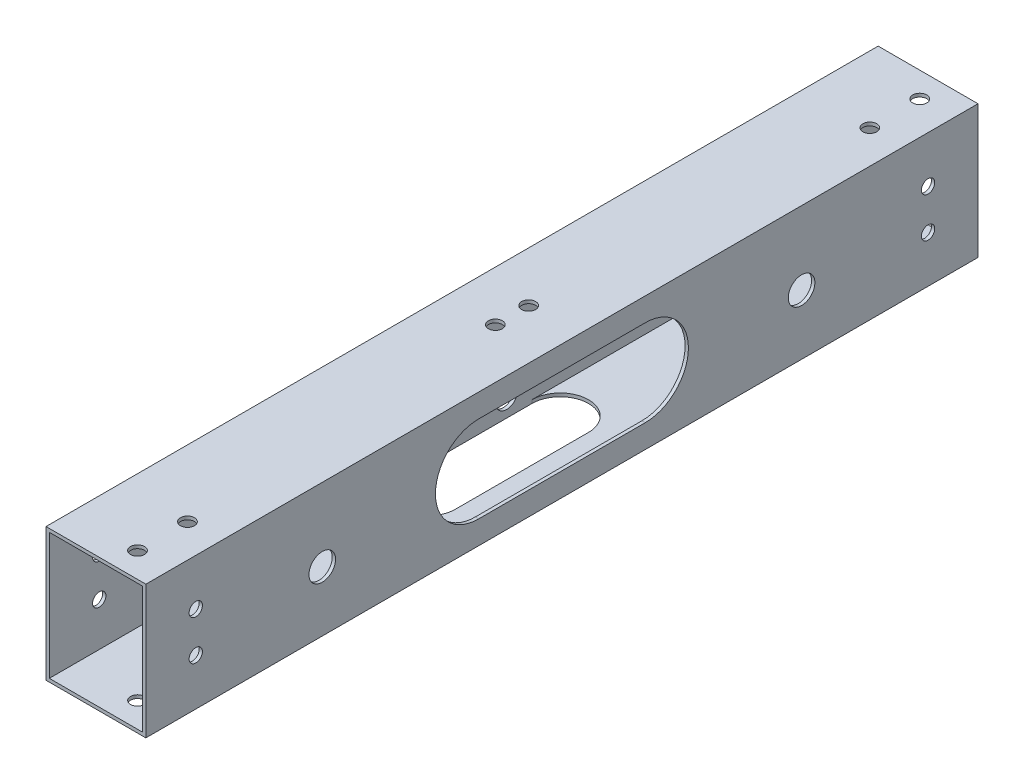
SolidWorks part; units mm, degrees
material "6061 合金"
ref_plane "前视基准面" through (0, 0, 0) normal (0, 0, 1) x (1, 0, 0)
ref_plane "上视基准面" through (0, 0, 0) normal (0, 1, 0) x (1, 0, 0)
ref_plane "右视基准面" through (0, 0, 0) normal (1, 0, 0) x (0, 0, -1)
other "Configuration Table"
sketch "草图1" plane through (0, 0, 0) normal (0, 0, 1) x (1, 0, 0)
  line L0 (15, -20) -> (15, 20)
  line L1 (15, 20) -> (-15, 20)
  line L2 (-15, 20) -> (-15, -20)
  line L3 (-15, -20) -> (15, -20)
  line L4 (14, 19) -> (-14, 19)
  line L5 (14, -19) -> (14, 19)
  line L6 (-14, -19) -> (14, -19)
  line L7 (-14, 19) -> (-14, -19)
extrude "凸台-拉伸1" add sketch "草图1" along normal blind 250
sketch "草图3" plane through (0, 20, 0) normal (0, 1, 0) x (1, 0, 0)
  line L0 (15, 0) -> (-15, 0) construction
  line L2 (-15, -125) -> (78.6025, -125) construction
  line L4 (-15, -250) -> (-15, 0) construction
  circle A0 centre (5, -7.5) radius 2.1
  circle A1 centre (5, -22.5) radius 2.1
  circle A4 centre (5, -227.5) radius 2.1
  circle A5 centre (5, -242.5) radius 2.1
  circle A6 centre (0, -120) radius 2.1
  circle A7 centre (0, -130) radius 2.1
  dimension "D1" = 4.2
  dimension "D2" = 7.5
  dimension "D4" = 20
  dimension "D5" = 4.2
  dimension "D6" = 10
  dimension "D3" = 2
extrude "切除-拉伸1" cut sketch "草图3" against normal blind 250
sketch "草图4" plane through (15, 0, 0) normal (1, 0, 0) x (0, 0, -1)
  line L0 (-250, 20) -> (0, 20) construction
  line L1 (0, -20) -> (0, 20) construction
  line L2 (-125, 20) -> (-125, -104.7599) construction
  circle A0 centre (-53, -2) radius 4
  circle A1 centre (-197, -2) radius 4
  dimension "D1" = 8
  dimension "D2" = 22
  dimension "D3" = 53
extrude "切除-拉伸2" cut sketch "草图4" against normal blind 250
sketch "草图5" plane through (-15, 0, 0) normal (-1, 0, 0) x (0, 0, 1)
  line L0 (250, 20) -> (0, 20) construction
  circle A0 centre (125, -2) radius 7
  dimension "D1" = 22
  dimension "D2" = 14
extrude "切除-拉伸3" cut sketch "草图5" against normal blind 250
sketch "草图6" plane through (0, -20, 0) normal (0, -1, 0) x (1, 0, 0)
  line L0 (-15, 250) -> (-15, 0) construction
  line L2 (-14, 145) -> (-14, 105)
  line L4 (3, 145) -> (3, 105)
  line L5 (-15, 125) -> (57.9688, 125) construction
  line L6 (15, 250) -> (15, 0) construction
  arc A0 (3, 145) -> (-14, 145) centre (-5.5, 145) ccw
  arc A1 (-14, 105) -> (3, 105) centre (-5.5, 105) ccw
  dimension "D4" = 20
  dimension "D5" = 8.5
  dimension "D7" = 20.5
  dimension "D8" = 8.5
  dimension "D1" = 17
  dimension "D2" = 1
  dimension "D3" = 40
  dimension "D6" = 12
extrude "切除-拉伸4" cut sketch "草图6" against normal blind 20
sketch "草图7" plane through (15, 0, 0) normal (1, 0, 0) x (0, 0, -1)
  line L0 (-125, 20) -> (-125, -74.6216) construction
  line L1 (-250, 20) -> (0, 20) construction
  line L2 (-150, 0) -> (-100, 0) construction
  line L3 (-150, 13) -> (-100, 13)
  line L4 (-150, -13) -> (-100, -13)
  arc A0 (-150, 13) -> (-150, -13) centre (-150, 0) ccw
  arc A1 (-100, -13) -> (-100, 13) centre (-100, 0) ccw
  point P8 (-125, 0)
  dimension "D2" = 25
  dimension "D3" = 13
  dimension "D1" = 50
extrude "切除-拉伸6" cut sketch "草图7" against normal blind 22
sketch "草图8" plane through (-15, 0, 0) normal (-1, 0, 0) x (0, 0, 1)
  line L0 (125, 20) -> (125, -55.4072) construction
  line L1 (250, 20) -> (0, 20) construction
  line L2 (250, -20) -> (0, -20) construction
  circle A0 centre (112.625, -14.5) radius 3.25
  circle A1 centre (137.375, -14.5) radius 3.25
  circle A2 centre (112.625, 10.25) radius 3.25
  circle A3 centre (137.375, 10.25) radius 3.25
  dimension "D1" = 24.75
  dimension "D2" = 5.5
  dimension "D4" = 24.75
  dimension "D5" = 6.5
  dimension "D3" = 2
extrude "切除-拉伸7" cut sketch "草图8" against normal blind 22
sketch "草图9" plane through (15, 0, 0) normal (1, 0, 0) x (0, 0, -1)
  line L1 (0, -20) -> (0, 20) construction
  line L2 (-15, 6) -> (-15, -6) construction
  line L3 (-125, 20) -> (-125, -94.4562) construction
  line L4 (-250, 20) -> (0, 20) construction
  line L5 (-235, 6) -> (-235, -6) construction
  line L6 (-250, -20) -> (0, -20) construction
  circle A0 centre (-15, 6) radius 2
  circle A1 centre (-15, -6) radius 2
  circle A2 centre (-235, -6) radius 2
  circle A3 centre (-235, 6) radius 2
  dimension "D1" = 4
  dimension "D2" = 4
  dimension "D3" = 14
  dimension "D4" = 12
  dimension "D5" = 15
extrude "切除-拉伸8" cut sketch "草图9" against normal blind 36
